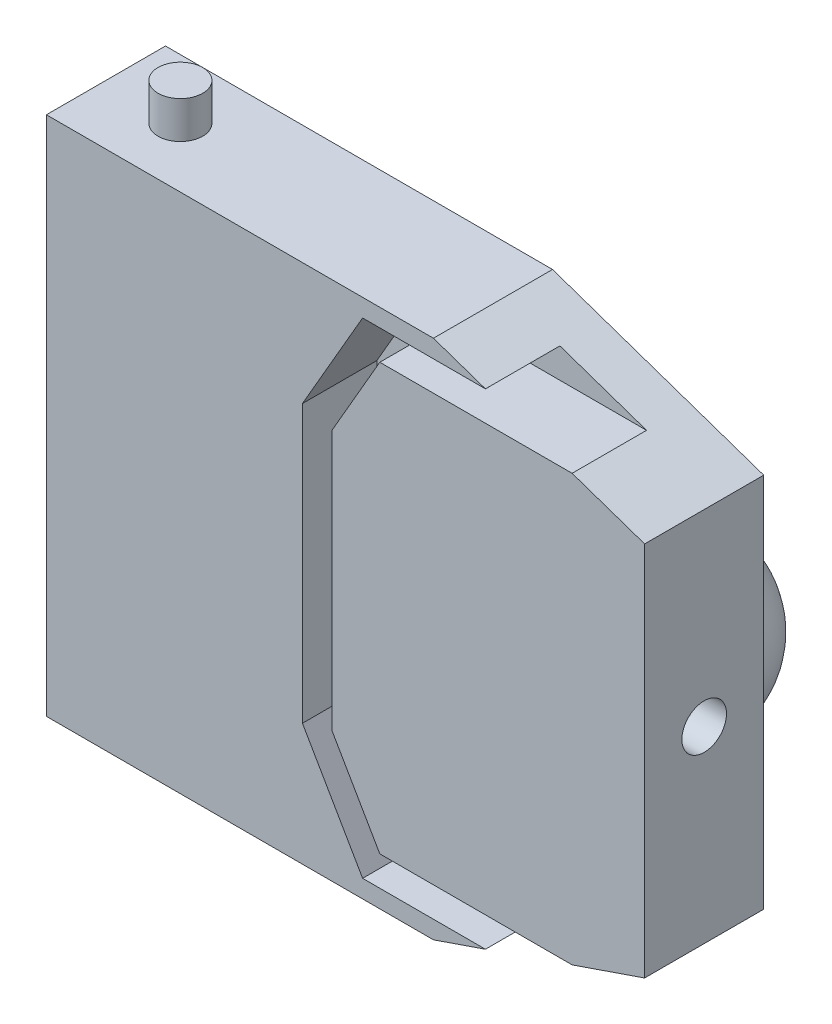
SolidWorks part; units mm, degrees
ref_plane "Front Plane" through (0, 0, 0) normal (0, 0, 1) x (1, 0, 0)
ref_plane "Top Plane" through (0, 0, 0) normal (0, 1, 0) x (1, 0, 0)
ref_plane "Right Plane" through (0, 0, 0) normal (1, 0, 0) x (0, 0, -1)
sketch "Sketch1" plane through (0, 0, 0) normal (0, 0, 1) x (1, 0, 0)
  line L8 (0, 0) -> (-260, 0)
  line L9 (-260, 0) -> (-260, -350)
  line L10 (-260, -350) -> (0, -350)
  line L11 (0, 0) -> (141.8631, -48.7326)
  line L12 (141.8631, -48.7326) -> (141.8631, -301.2674)
  line L13 (141.8631, -301.2674) -> (0, -350)
  point P6 (141.8631, -175)
  point P7 (-260, -175)
  dimension "D2" = 260
  dimension "D3" = 150
  dimension "D1" = 350
  dimension "D4" = 252.5348
extrude "Boss-Extrude1" add sketch "Sketch1" along normal blind 80
sketch "Sketch2" plane through (0, -350, 0) normal (0, -1, 0) x (1, 0, 0)
  line L0 (-260, 40) -> (0, 40) construction
  line L1 (-260, 80) -> (-260, 0) construction
  line L3 (-210, 80) -> (-210, 0) construction
  line L4 (-260, 80) -> (0, 80) construction
  line L5 (-260, 0) -> (0, 0) construction
  line L6 (0, 80) -> (0, 0) construction
  circle A0 centre (-210, 40) radius 15
  dimension "D2" = 30
  dimension "D1" = 50
  dimension "D3" = 50
extrude "Boss-Extrude2" add sketch "Sketch2" along normal blind 25 from surface starting at face at (-130, -350, 40)
extrude "Boss-Extrude3" add sketch "Sketch2<2>" against normal blind 25 from surface starting at face at (-130, 0, 40)
sketch "Sketch2<2>" plane through (0, -350, 0) normal (0, -1, 0) x (1, 0, 0) same geometry as "Sketch2"
sketch "Sketch3" plane through (0, 0, 0) normal (0, 0, -1) x (-1, 0, 0)
  line L0 (-141.8631, -175) -> (260, -175) construction
  line L1 (260, 0) -> (260, -350) construction
  line L2 (-11.8631, -175) -> (-131.8631, -175)
  line L3 (-141.8631, -301.2674) -> (-141.8631, -48.7326) construction
  arc A1 (-11.8631, -175) -> (-131.8631, -175) centre (-71.8631, -175) ccw
  dimension "D1" = 60
  dimension "D2" = 70
sketch "Sketch4" plane through (141.8631, 0, 0) normal (1, 0, 0) x (0, 0, -1)
  line L0 (0, -301.2674) -> (0, -48.7326) construction
  line L1 (-80, -48.7326) -> (0, -48.7326) construction
  circle A0 centre (-40, -175) radius 15
  point P5 (0, -175)
  point P9 (-40, -48.7326)
  dimension "D1" = 30
extrude "Cut-Extrude1" cut sketch "Sketch4" against normal blind 30
sketch "Sketch5" plane through (0, 0, 80) normal (0, 0, 1) x (1, 0, 0)
  line L0 (34.9326, -338) -> (-47.5855, -338)
  line L1 (0, -350) -> (141.8631, -301.2674) construction
  line L2 (-260, -350) -> (0, -350) construction
  line L3 (-260, -175) -> (141.8631, -175) construction
  line L4 (-47.5855, -338) -> (-88, -268)
  line L5 (-260, 0) -> (-260, -350) construction
  line L6 (141.8631, -301.2674) -> (141.8631, -48.7326) construction
  line L7 (-47.5855, -12) -> (-88, -82)
  line L8 (34.9326, -12) -> (-47.5855, -12)
  line L9 (-88, -268) -> (-88, -82)
  line L10 (93.1536, -318) -> (-36.0385, -318)
  line L11 (-36.0385, -318) -> (-68, -262.641)
  line L12 (-68, -262.641) -> (-68, -87.359)
  line L13 (-68, -87.359) -> (-36.0385, -32)
  line L14 (-36.0385, -32) -> (93.1536, -32)
  line L15 (141.8631, -48.7326) -> (0, 0) construction
  line L16 (34.9326, -338) -> (93.1536, -318)
  line L17 (34.9326, -12) -> (93.1536, -32)
  dimension "D1" = 12
  dimension "D3" = 120
  dimension "D4" = 70
  dimension "D2" = 172
  dimension "D5" = 20
  dimension "D6" = 20
  dimension "D7" = 20
  dimension "D8" = 20
  dimension "D9" = 20
extrude "Cut-Extrude3" cut sketch "Sketch5" against normal blind 50 contours L11 L12 L13 L14 L17 L8 L7 L9 L4 L0 L16 L10
ref_point "Point1"
revolve "Revolve1" add sketch "Sketch3" angle 180 about L0
